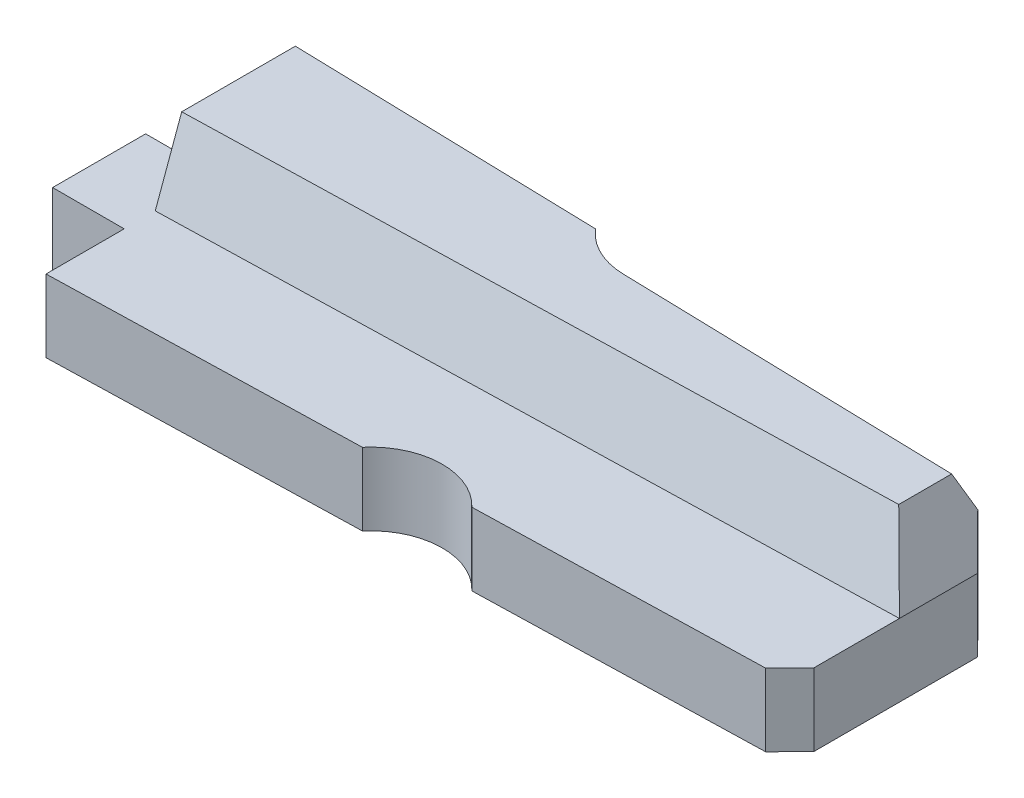
SolidWorks part; units mm, degrees
ref_plane "Front Plane" through (0, 0, 0) normal (0, 0, 1) x (1, 0, 0)
ref_plane "Top Plane" through (0, 0, 0) normal (0, 1, 0) x (1, 0, 0)
ref_plane "Right Plane" through (0, 0, 0) normal (1, 0, 0) x (0, 0, -1)
sketch "Sketch1" plane through (0, 0, 0) normal (0, 1, 0) x (1, 0, 0)
  line L0 (-14.914, 10.7961) -> (-14.914, -10.7339)
  line L1 (-14.914, -10.7339) -> (57.586, -8.8214)
  line L2 (57.586, -8.8214) -> (57.586, 8.8786)
  line L3 (57.586, 8.8786) -> (-14.914, 10.7961)
  dimension "D1" = 21.53
  dimension "D2" = 17.7
  dimension "D3" = 72.5
  dimension "D4" = 88.485
extrude "Boss-Extrude1" add sketch "Sketch1" along normal blind 6.08
sketch "Sketch2" plane through (0, 6.08, 0) normal (0, 1, 0) x (1, 0, 0)
  line L2 (-13.064, 10.7961) -> (-13.064, -10.7339)
  line L3 (-13.064, 10.7472) -> (-13.064, -1.5219)
  line L5 (-15.1556, -1.5771) -> (57.3444, 0.3354)
  line L6 (-13.064, -1.5219) -> (57.586, 0.3418)
  line L8 (57.586, 8.8786) -> (-14.914, 10.7961)
  line L9 (57.586, 8.8786) -> (-13.064, 10.7472)
  line L11 (57.586, -8.8214) -> (57.586, 8.8786)
  line L12 (57.586, 0.3418) -> (57.586, 8.8786)
  dimension "D1" = 1.85
  dimension "D2" = 9.16
  dimension "D3" = 0
  dimension "D4" = 0
extrude "Boss-Extrude2" add sketch "Sketch2" along normal blind 6.09
ref_plane "Plane1" through (0.0789, 1.0895, 2.9922) normal (0.0248, 0.342, 0.9394) x (0.9997, 0, -0.0264)
ref_axis "Axis1" through (-13.064, 12.17, -0.6954) along (0.9997, 0, -0.0264)
sketch "Sketch4" plane through (0.0789, 1.0895, 2.9922) normal (0.0248, 0.342, 0.9394) x (0.9997, 0, -0.0264)
  line L2 (-13.0996, 5.3108) -> (57.5749, 5.3108)
  line L3 (-13.0996, 5.3108) -> (57.8001, 5.3108)
  line L5 (-13.0996, 11.0335) -> (-13.0996, 5.3108)
  line L6 (-13.0996, 14.6247) -> (-13.0996, 5.3108)
  line L7 (-13.0996, 14.6247) -> (57.8001, 14.6247)
  line L10 (57.8001, 13.9523) -> (57.8001, 2.5162) construction
  line L11 (57.8001, 13.9523) -> (57.8001, 2.5162)
  line L12 (57.8001, 14.6247) -> (57.8001, 5.3108)
  dimension "D1" = 0
  dimension "D2" = 0
  dimension "D3" = 0
extrude "Cut-Extrude4" cut sketch "Sketch4" along normal blind 13.09 contours L3 L12 L7 L6
ref_plane "Plane2" through (52.8037, 19.219, 0) normal (0.9397, 0.342, 0) x (0, 0, -1)
sketch "Sketch5" plane through (52.8037, 19.219, 0) normal (0.9397, 0.342, 0) x (0, 0, -1)
  line L1 (-14.2418, -13.9822) -> (-14.2418, -1.7479)
  line L2 (-8.8214, -13.9822) -> (0.3418, -13.9822)
  line L3 (-14.2418, -13.9822) -> (15.0642, -13.9822)
  line L4 (-14.2418, -1.7479) -> (15.0642, -1.7479)
  line L5 (15.0642, -1.7479) -> (15.0642, -13.9822)
  dimension "D1" = 0
extrude "Cut-Extrude5" cut sketch "Sketch5" along normal blind 19.09
sketch "Sketch6" plane through (0, 0, 0) normal (0, -1, 0) x (1, 0, 0)
  line L0 (-14.914, 10.7339) -> (-14.914, 8.7339)
  line L1 (-14.914, -10.7961) -> (-14.914, 10.7339) construction
  line L2 (-14.914, 8.7339) -> (-12.914, 10.6811)
  line L3 (-14.914, 10.7339) -> (57.586, 8.8214) construction
  line L4 (-12.914, 10.6811) -> (-14.914, 10.7339)
  line L5 (-14.914, -10.7961) -> (-12.914, -10.7432)
  line L6 (57.586, -8.8786) -> (-14.914, -10.7961) construction
  line L7 (-12.914, -10.7432) -> (-14.914, -8.7961)
  line L8 (-14.914, -8.7961) -> (-14.914, -10.7961)
  line L9 (55.5866, 8.8741) -> (57.586, 8.8214)
  line L10 (57.586, 8.8214) -> (57.586, 6.8214)
  line L11 (57.586, 8.8214) -> (57.586, -8.8786) construction
  line L12 (57.586, 6.8214) -> (55.5866, 8.8741)
  line L13 (57.586, -8.8786) -> (57.586, -6.8786)
  line L14 (57.586, -6.8786) -> (55.586, -8.9315)
  line L15 (55.586, -8.9315) -> (57.586, -8.8786)
  line L16 (27.216, 19.304) -> (27.216, -14.3897) construction
  circle A1 centre (27.216, 13.6239) radius 6
  circle A2 centre (27.216, -13.6832) radius 6
  dimension "D11" = 12
  dimension "D12" = 12
  dimension "D1" = 2
  dimension "D2" = 2
  dimension "D3" = 2
  dimension "D4" = 2
  dimension "D5" = 2
  dimension "D6" = 2
  dimension "D7" = 2
  dimension "D8" = 2
  dimension "D9" = 42.13
  dimension "D10" = 4
  dimension "D13" = 4
extrude "Cut-Extrude6" cut sketch "Sketch6" against normal through all
ref_plane "Plane3" through (0, 7.78, 0) normal (0, 1, 0) x (1, 0, 0)
ref_axis "Axis2" through (360.074, 7.78, -0.8784) along (-0.9997, 0, -0.0264)
ref_plane "Plane4" through (0.3053, 5.2601, -11.542) normal (0.0241, 0.4146, -0.9097) x (-0.9997, 0.01, -0.0219)
sketch "Sketch7" plane through (0.3053, 5.2601, -11.542) normal (0.0241, 0.4146, -0.9097) x (-0.9997, 0.01, -0.0219)
  line L0 (-26.9217, 7.8879) -> (-26.9217, 3.0644)
  line L1 (-359.8729, 6.7147) -> (-60.2731, 3.43) construction
  line L2 (-26.9217, 3.0644) -> (-63.5754, 3.4662)
  line L3 (-63.5754, 3.4662) -> (-63.5754, 10.3897)
  line L4 (-63.5754, 10.3897) -> (-26.9217, 9.9878)
  line L5 (-26.9217, 9.9878) -> (-26.9217, 7.8879)
  ellipse E0 centre (-26.7871, 5.3996) end of major axis (-20.7874, 5.3339) minor radius 2.4875 (-22.297, 7.0089) -> (-31.2408, 7.1069) ccw construction
extrude "Cut-Extrude7" cut sketch "Sketch7" along normal blind 11.09
ref_plane "Cut surface" through (-3.214, 0, 0) normal (-1, 0, 0) x (0, 0, 1)
sketch "Sketch10" plane through (-3.214, 0, 0) normal (-1, 0, 0) x (0, 0, 1)
  line L1 (-17.6293, 15.2246) -> (18.4681, 15.2246)
  line L2 (-17.6293, 15.2246) -> (-17.6293, -7.7626)
  line L3 (-17.6293, -7.7626) -> (18.4681, -7.7626)
  line L4 (18.4681, 15.2246) -> (18.4681, -7.7626)
extrude "Cut-Extrude11" cut sketch "Sketch10" along normal through all
sketch "Sketch12" plane through (-3.214, 0, 0) normal (-1, 0, 0) x (0, 0, 1)
  line L1 (-3.9307, 6.08) -> (3.8693, 6.08)
  line L2 (-3.9307, 6.08) -> (-3.9307, 0)
  line L3 (-3.9307, 0) -> (3.8693, 0)
  line L4 (3.8693, 6.08) -> (3.8693, 0)
  line L5 (-10.4867, 0) -> (10.4253, 0) construction
  line L6 (-0.0307, -3.669) -> (-0.0307, 11.8159) construction
  line L8 (1.2621, 6.08) -> (10.4253, 6.08) construction
  line L11 (-10.4867, 12.17) -> (-10.4867, 0) construction
  line L12 (10.4253, 0) -> (10.4253, 6.08) construction
  dimension "D1" = 7.8
  dimension "D4" = 0
extrude "Boss-Extrude4" add sketch "Sketch12" along normal blind 6
